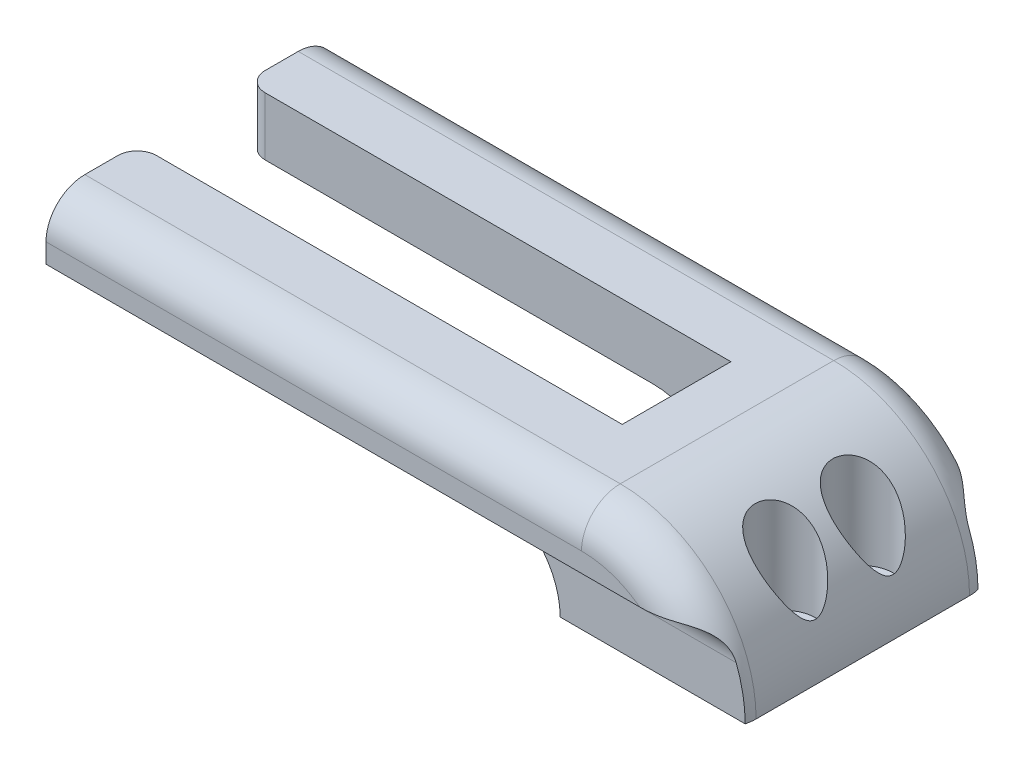
SolidWorks part; units mm, degrees
ref_plane "Front Plane" through (0, 0, 0) normal (0, 0, 1) x (1, 0, 0)
ref_plane "Top Plane" through (0, 0, 0) normal (0, 1, 0) x (1, 0, 0)
ref_plane "Right Plane" through (0, 0, 0) normal (1, 0, 0) x (0, 0, -1)
sketch "Sketch1" plane through (0, 0, 0) normal (0, 0, 1) x (1, 0, 0)
  line L1 (-37, 27) -> (-175, 27)
  line L2 (-175, 27) -> (-175, 12)
  line L3 (-175, 12) -> (-50, 12)
  line L4 (-50, 12) -> (-50, -8)
  line L5 (-50, -8) -> (-2, -8)
  arc A0 (-2, -8) -> (-37, 27) centre (-37, -8) ccw
  point P9 (0, 32)
  dimension "D5" = 35
  dimension "D1" = 35
  dimension "D2" = 20
  dimension "D3" = 48
  dimension "D4" = 125
extrude "Boss-Extrude1" add sketch "Sketch1" along normal mid plane 75
sketch "Sketch2" plane through (0, -8, 0) normal (0, -1, 0) x (1, 0, 0)
  line L0 (-50, 14) -> (-50, -14)
  line L1 (-50, 37.5) -> (-50, -37.5) construction
  line L2 (-50, -14) -> (-175, -14)
  line L3 (-175, 37.5) -> (-175, -37.5) construction
  line L4 (-175, -14) -> (-175, 14)
  line L5 (-175, 14) -> (-50, 14)
  line L6 (0, 0) -> (-89.4399, 0) construction
  point P5 (-50, 0)
  dimension "D1" = 28
extrude "Cut-Extrude1" cut sketch "Sketch2" against normal blind 60
sketch "Sketch3" plane through (-50, 0, 0) normal (-1, 0, 0) x (0, 0, 1)
  line L1 (37.5, -8) -> (-37.5, -8) construction
  line L2 (-30, -8) -> (-37.5, -8)
  line L3 (-37.5, -8) -> (-37.5, 12)
  line L4 (-37.5, 12) -> (-30, 12)
  line L5 (-14, 12) -> (-37.5, 12) construction
  line L6 (-30, 12) -> (-30, -8)
  line L7 (30, -8) -> (37.5, -8)
  line L8 (37.5, 12) -> (37.5, -8) construction
  line L9 (37.5, -8) -> (37.5, 12)
  line L10 (37.5, 12) -> (30, 12)
  line L11 (37.5, 12) -> (14, 12) construction
  line L12 (30, 12) -> (30, -8)
  point P6 (0, 0)
  dimension "D1" = 60
extrude "Cut-Extrude2" cut sketch "Sketch3" against normal blind 60
sketch "Sketch4" plane through (0, 27, 0) normal (0, 1, 0) x (1, 0, 0)
  line L0 (-8.2772, 37.5) -> (-37, 37.5) construction
  line L1 (0, 0) -> (-68.7276, 0) construction
  line L2 (-37, -37.5) -> (-8.2772, -37.5) construction
  line L3 (-8.2772, -37.5) -> (-8.2772, -30) construction
  line L4 (-8.2772, -30) -> (0, -30) construction
  line L5 (0, -30) -> (0, 30) construction
  line L6 (-50, 14) -> (-50, -14) construction
  circle A0 centre (-12, -10) radius 3
  circle A1 centre (-12, -10) radius 7.75
  circle A2 centre (-12, 10) radius 7.75
  circle A3 centre (-12, 10) radius 3
  dimension "D2" = 6
  dimension "D3" = 15.5
  dimension "D1" = 50
  dimension "D4" = 10
  dimension "D5" = 12
extrude "Cut-Extrude3" cut sketch "Sketch4" against normal blind 60 contours A3 | A0
extrude "Cut-Extrude4" cut sketch "Sketch4<3>" against normal blind 30 contours A2 | A1
sketch "Sketch4<3>" plane through (0, 27, 0) normal (0, 1, 0) x (1, 0, 0) same geometry as "Sketch4"
fillet "Fillet1" radius 20 1 edges at (-50, 12, -22)
fillet "Fillet2" radius 7.5 2 edges at (-39.1386, 12, 30) (-39.1386, 12, -30)
fillet "Fillet3" radius 10 4 edges at (-20.7981, 23.0242, -37.5) (-20.7981, 23.0242, 37.5) (-106, 27, -37.5) (-106, 27, 37.5)
fillet "Fillet4" radius 5 2 edges at (-175, 19.5, -14) (-175, 19.5, 14)
